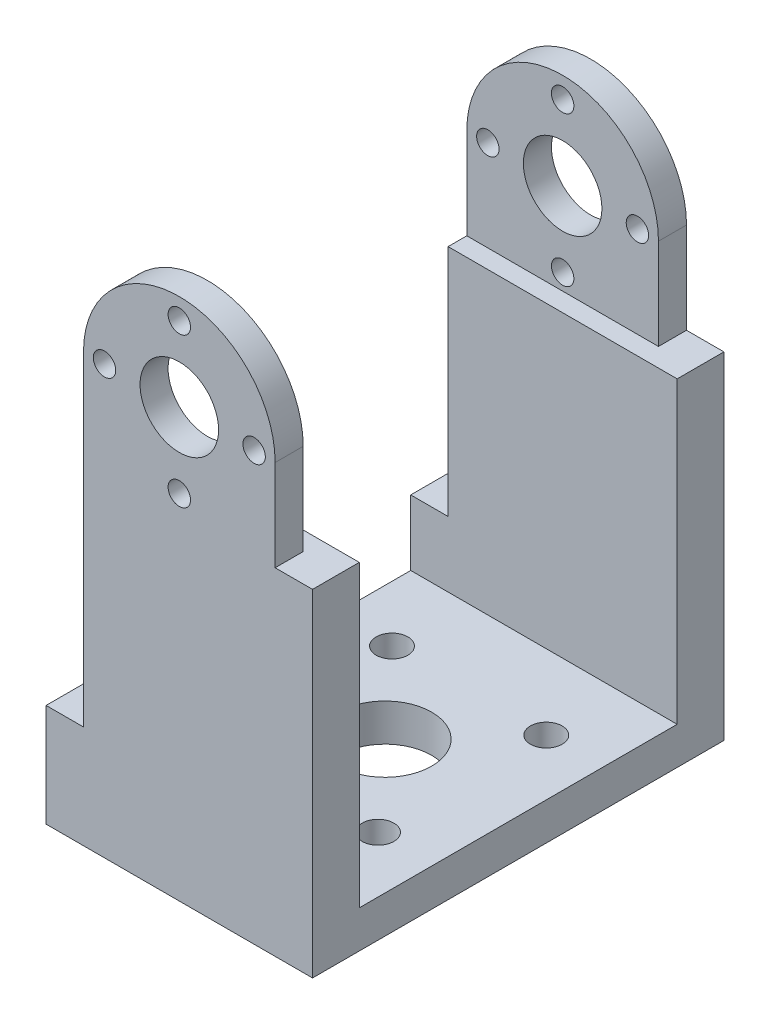
SolidWorks part; units mm, degrees
ref_plane "Front Plane" through (0, 0, 0) normal (0, 0, 1) x (1, 0, 0)
ref_plane "Top Plane" through (0, 0, 0) normal (0, 1, 0) x (1, 0, 0)
ref_plane "Right Plane" through (0, 0, 0) normal (1, 0, 0) x (0, 0, -1)
sketch "Sketch1" plane through (0, 0, 0) normal (0, 0, 1) x (1, 0, 0)
  line L0 (0, 0) -> (0, -100) construction
  line L1 (0, -100) -> (-70, -100) construction
  line L2 (-10.25, -60) -> (-70, -60) construction
  line L4 (-10.25, 0) -> (10.25, 0)
  line L5 (-10.25, 0) -> (-10.25, -60)
  line L7 (10.25, 0) -> (10.25, -60)
  line L8 (-10.25, 0) -> (10.25, 0)
  line L9 (-10.25, 0) -> (-10.25, -100)
  line L10 (-10.25, -100) -> (10.25, -100)
  line L11 (10.25, 0) -> (10.25, -100)
  circle A0 centre (0, 0) radius 10.25
  circle A1 centre (0, 0) radius 8
  circle A2 centre (0, 0) radius 4.2
  circle A3 centre (0, 8) radius 1.2
  circle A4 centre (8, 0) radius 1.2
  circle A5 centre (0, -8) radius 1.2
  circle A6 centre (-8, 0) radius 1.2
  point P16 (0, 0)
  dimension "D1" = 20.5
  dimension "D2" = 16
  dimension "D3" = 8.4
  dimension "D4" = 2.4
  dimension "D6" = 100
  dimension "D7" = 70
  dimension "D8" = 40
  dimension "D5" = 4
extrude "Boss-Extrude1" add sketch "Sketch1" along normal blind 22 and the other way blind 22 contours A0 L5 L7 | A6 L4 A0 A4 A1 A5 | A6 A1 A5 A4 L4 A2 | A6 L4 A2 A4 A1 A3 | A6 A1 A3 A4 L4 A0 region at (8.972, 1.0478, 0) region at (9.725, -0.2292, 0) region at (6.9906, -0.9364, 0) region at (5.5, 0.1769, 0) region at (0, -53.9967, 0)
sketch "Sketch2" plane through (-10.25, 0, 0) normal (-1, 0, 0) x (0, 0, 1)
  line L0 (22, 10.25) -> (-22, 10.25) construction
  line L1 (-19, 10.25) -> (19, 10.25)
  line L2 (-19, 10.25) -> (-19, -9.75)
  line L3 (-19, -9.75) -> (19, -9.75)
  line L4 (19, 10.25) -> (19, -9.75)
  line L5 (22, 0) -> (22, 10.25) construction
  line L6 (-22, 10.25) -> (-22, 0) construction
  dimension "D1" = 3
  dimension "D2" = 3
  dimension "D3" = 20
extrude "Cut-Extrude1" cut sketch "Sketch2" against normal through all
sketch "Sketch3" plane through (0, -9.75, 0) normal (0, 1, 0) x (1, 0, 0)
  line L1 (-10.25, 22) -> (-17.25, 22)
  line L2 (-10.25, 22) -> (-10.25, -22)
  line L3 (-10.25, -22) -> (-17.25, -22)
  line L4 (-17.25, 22) -> (-17.25, -22)
  line L5 (10.25, 22) -> (17.25, 22)
  line L6 (10.25, 22) -> (10.25, -22)
  line L7 (10.25, -22) -> (17.25, -22)
  line L8 (17.25, 22) -> (17.25, -22)
  dimension "D1" = 7
  dimension "D2" = 7
extrude "Boss-Extrude2" add sketch "Sketch3" against normal blind 36
sketch "Sketch5" plane through (-17.25, 0, 0) normal (-1, 0, 0) x (0, 0, 1)
  line L0 (-22, -9.75) -> (22, -9.75) construction
  line L1 (-17, -9.75) -> (17, -9.75)
  line L2 (-17, -9.75) -> (-17, -59.75)
  line L3 (-17, -59.75) -> (17, -59.75)
  line L4 (17, -9.75) -> (17, -59.75)
  line L8 (-19, 0) -> (-19, -9.75) construction
  dimension "D1" = 34
  dimension "D2" = 2
  dimension "D3" = 50
extrude "Cut-Extrude3" cut sketch "Sketch5" against normal through all
sketch "Sketch6" plane through (0, 0, 22) normal (0, 0, 1) x (1, 0, 0)
  line L1 (10.25, -45.75) -> (-10.25, -45.75)
  line L2 (10.25, -45.75) -> (10.25, -100)
  line L3 (10.25, -100) -> (-10.25, -100)
  line L4 (-10.25, -45.75) -> (-10.25, -100)
extrude "Cut-Extrude4" cut sketch "Sketch6" against normal through all
sketch "Sketch20" plane through (0, -45.75, 0) normal (0, -1, 0) x (1, 0, 0)
  line L1 (-17.25, 22) -> (17.25, 22)
  line L2 (-17.25, 22) -> (-17.25, -22)
  line L3 (-17.25, -22) -> (17.25, -22)
  line L4 (17.25, 22) -> (17.25, -22)
  line L5 (-17.25, 17) -> (17.25, 17) construction
  line L6 (17.25, -17) -> (-17.25, -17) construction
  line L8 (-14.25, 17) -> (14.25, 17)
  line L9 (-14.25, 17) -> (-14.25, -17)
  line L10 (-14.25, -17) -> (14.25, -17)
  line L11 (14.25, 17) -> (14.25, -17)
  circle A0 centre (0, 0) radius 5
  circle A2 centre (-8.25, 9) radius 1.7
  circle A3 centre (8.25, 9) radius 1.7
  circle A4 centre (8.25, -9) radius 1.7
  circle A5 centre (-8.25, -9) radius 1.7
  line M7 (-17.25, 17) -> (17.25, 17)
  dimension "D1" = 3
  dimension "D2" = 3
  dimension "D3" = 6
  dimension "D4" = 8
  dimension "D5" = 2
  dimension "D6" = 2
extrude "Boss-Extrude5" add sketch "Sketch20" against normal blind 4 contours L11 L9 L10 A5 A4 A3 A2 A0 M7 region at (0, -45.75, 16.5564)
sketch "Sketch21" plane through (0, 0, -22) normal (0, 0, -1) x (-1, 0, 0)
  line L0 (-17.25, -45.75) -> (17.25, -45.75) construction
  line L1 (-17.25, -9.75) -> (-14.25, -9.75)
  line L2 (-17.25, -9.75) -> (-17.25, -45.75)
  line L3 (-17.25, -45.75) -> (-14.25, -45.75)
  line L4 (-14.25, -9.75) -> (-14.25, -45.75)
  line L6 (17.25, -9.75) -> (14.25, -9.75)
  line L7 (17.25, -9.75) -> (17.25, -45.75)
  line L8 (17.25, -45.75) -> (14.25, -45.75)
  line L9 (14.25, -9.75) -> (14.25, -45.75)
  dimension "D1" = 3
  dimension "D2" = 3
extrude "Cut-Extrude12" cut sketch "Sketch21" against normal through all
sketch "Sketch22" plane through (0, 0, -22) normal (0, 0, -1) x (-1, 0, 0)
  line L0 (-14.25, -45.75) -> (-14.25, -9.75) construction
  line L1 (-10.25, -9.75) -> (-14.25, -9.75)
  line L2 (-10.25, -9.75) -> (-10.25, -34.75)
  line L3 (-10.25, -34.75) -> (-14.25, -34.75)
  line L4 (-14.25, -9.75) -> (-14.25, -34.75)
  line L5 (14.25, -9.75) -> (14.25, -45.75) construction
  line L6 (10.25, -9.75) -> (14.25, -9.75)
  line L7 (10.25, -9.75) -> (10.25, -34.75)
  line L8 (10.25, -34.75) -> (14.25, -34.75)
  line L9 (14.25, -9.75) -> (14.25, -34.75)
  dimension "D1" = 25
extrude "Cut-Extrude14" cut sketch "Sketch22" against normal through all contours L9 L8 L7 L6
